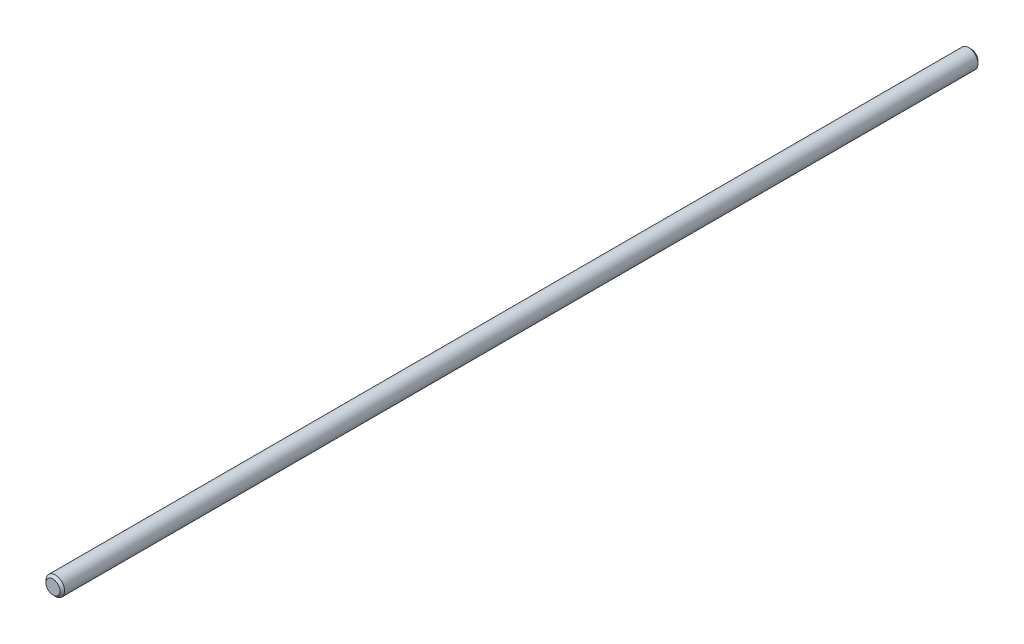
SolidWorks part; units mm, degrees
ref_plane "Front Plane" through (0, 0, 0) normal (0, 0, 1) x (1, 0, 0)
ref_plane "Top Plane" through (0, 0, 0) normal (0, 1, 0) x (1, 0, 0)
ref_plane "Right Plane" through (0, 0, 0) normal (1, 0, 0) x (0, 0, -1)
sketch "Sketch1" plane through (0, 0, 0) normal (0, 0, 1) x (1, 0, 0)
  circle A0 centre (0, 0) radius 4
  dimension "D1" = 8
extrude "Boss-Extrude1" add sketch "Sketch1" along normal blind 395
chamfer "Chamfer1" distance 1 angle 45 2 edges at (4, 0, 395) (4, 0, 0)
